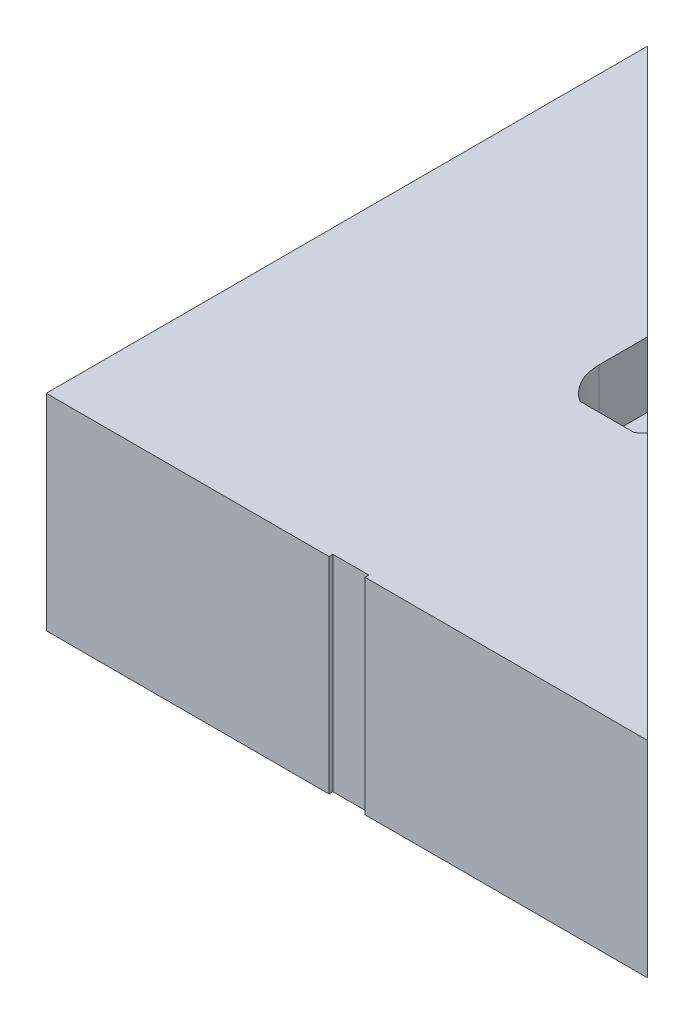
SolidWorks part; units mm, degrees
ref_plane "Front Plane" through (0, 0, 0) normal (0, 0, 1) x (1, 0, 0)
ref_plane "Top Plane" through (0, 0, 0) normal (0, 1, 0) x (1, 0, 0)
ref_plane "Right Plane" through (0, 0, 0) normal (1, 0, 0) x (0, 0, -1)
sketch "Sketch1" plane through (0, 0, 0) normal (0, 1, 0) x (1, 0, 0)
  line L1 (0, 0) -> (117, 0)
  line L2 (0, 0) -> (0, 117)
  line L3 (0, 117) -> (117, 117)
  line L4 (117, 0) -> (117, 117)
  dimension "D1" = 117
  dimension "D2" = 117
extrude "Boss-Extrude1" add sketch "Sketch1" along normal blind 40
sketch "Sketch2" plane through (0, 40, 0) normal (0, 1, 0) x (1, 0, 0)
  line L0 (58.5, 117) -> (58.5, 0) construction
  line L1 (117, 117) -> (0, 117) construction
  line L2 (0, 0) -> (117, 0) construction
  line L3 (0, 58.5) -> (117, 58.5) construction
  line L4 (0, 117) -> (0, 0) construction
  line L5 (117, 0) -> (117, 117) construction
  line L7 (68.025, 58.5) -> (48.975, 58.5)
  line L8 (68.025, 58.5) -> (68.025, 74.375)
  line L9 (68.025, 74.375) -> (48.975, 74.375)
  line L10 (48.975, 58.5) -> (48.975, 74.375)
  line L11 (53.2349, 66.4375) -> (63.7651, 66.4375)
  line L12 (53.2349, 66.4375) -> (53.2349, 50.5625)
  line L13 (53.2349, 50.5625) -> (63.7651, 50.5625)
  line L14 (63.7651, 66.4375) -> (63.7651, 50.5625)
  line L15 (53.2349, 66.4375) -> (63.7651, 50.5625) construction
  line L16 (53.2349, 50.5625) -> (63.7651, 66.4375) construction
  circle A0 centre (58.5, 58.5) radius 9.525
  point P22 (58.5, 50.5625)
  dimension "D1" = 19.05
  dimension "D2" = 19.05
  dimension "D3" = 7.9375
  dimension "D4" = 23.8125
extrude "Cut-Extrude1" cut sketch "Sketch2" against normal blind 12.7 contours A0 L8 L9 L10 | L7 A0 L14 | L12 A0 L7 | L14 L11 L12 L7 | L11 A0 | L14 A0 L7 | L7 A0 L12 | L14 L7 L12 L13
sketch "Sketch4" plane through (0, 0, 0) normal (0, -1, 0) x (1, 0, 0)
  line L0 (0, -117) -> (117, 0)
ref_point "Point1"
ref_axis "Axis1" through (58.5, 0, -58.5) along (0, -1, 0)
sketch "Sketch7" plane through (0, 0, 0) normal (0, -1, 0) x (1, 0, 0)
  line L5 (117, -117) -> (0, -117) construction
  line L10 (55, -116.25) -> (62, -116.25)
  line L11 (55, -116.25) -> (55, -117.75)
  line L12 (55, -117.75) -> (62, -117.75)
  line L13 (62, -116.25) -> (62, -117.75)
  line L14 (55, -116.25) -> (62, -117.75) construction
  line L15 (55, -117.75) -> (62, -116.25) construction
  point P0 (58.5, -117)
  dimension "D1" = 7
  dimension "D2" = 1.5
extrude "Cut-Extrude5" cut sketch "Sketch7" against normal through all
pattern_circular "CirPattern3" count 3 every 90 about axis through (58.5, 0, -58.5) along (0, -1, 0) of "Cut-Extrude5"
sketch "Sketch11" plane through (0, 0, 0) normal (0, -1, 0) x (1, 0, 0)
  line L0 (0, -117) -> (117, 0)
  line L1 (0, -117) -> (71.6403, -188.6403)
  line L2 (117, 0) -> (188.6403, -71.6403)
  line L3 (71.6403, -188.6403) -> (188.6403, -71.6403)
extrude "Cut-Extrude11" cut sketch "Sketch11" against normal through all
